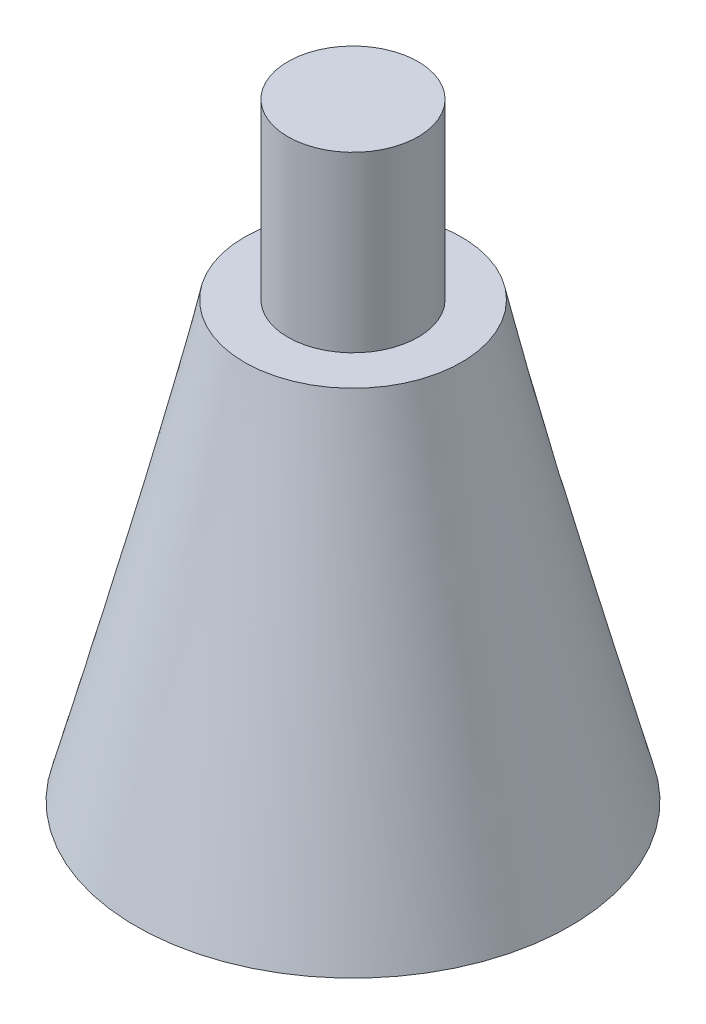
SolidWorks part; units mm, degrees
ref_plane "Front Plane" through (0, 0, 0) normal (0, 0, 1) x (1, 0, 0)
ref_plane "Top Plane" through (0, 0, 0) normal (0, 1, 0) x (1, 0, 0)
ref_plane "Right Plane" through (0, 0, 0) normal (1, 0, 0) x (0, 0, -1)
sketch "Sketch1" plane through (0, 0, 0) normal (0, 1, 0) x (1, 0, 0)
  circle A0 centre (0, 0) radius 3
  dimension "D1" = 6
extrude "Boss-Extrude1" add sketch "Sketch1" along normal blind 8
sketch "Sketch2" plane through (0, 0, 0) normal (0, -1, 0) x (1, 0, 0)
  circle A0 centre (0, 0) radius 5
  dimension "D1" = 10
ref_plane "Plane1" through (0, -20, 0) normal (0, -1, 0) x (-1, 0, 0)
sketch "Sketch3" plane through (0, -20, 0) normal (0, -1, 0) x (-1, 0, 0)
  circle A0 centre (0, 0) radius 10
  dimension "D1" = 20
loft "Loft1" add profiles "Sketch2", "Sketch3" connector at (0.6858, 0, 4.9527) connector at (-2.2672, -20, 9.7396)
